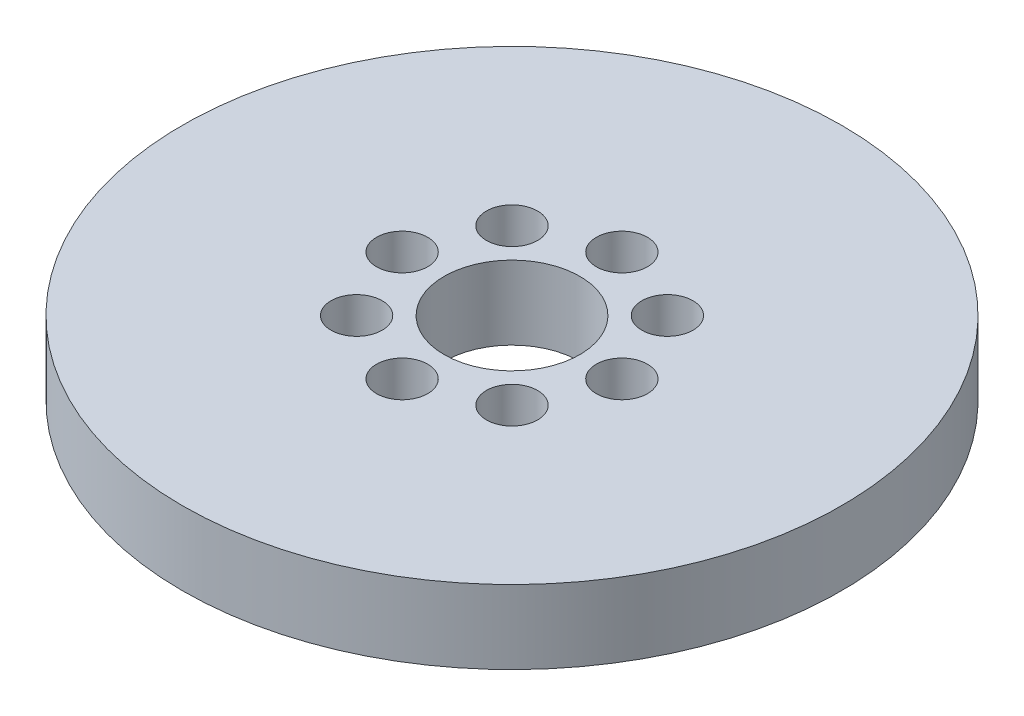
SolidWorks part; units mm, degrees
ref_plane "Front Plane" through (0, 0, 0) normal (0, 0, 1) x (1, 0, 0)
ref_plane "Top Plane" through (0, 0, 0) normal (0, 1, 0) x (1, 0, 0)
ref_plane "Right Plane" through (0, 0, 0) normal (1, 0, 0) x (0, 0, -1)
sketch "Sketch1" plane through (0, 0, 0) normal (0, 1, 0) x (1, 0, 0)
  circle A0 centre (0, 0) radius 85
  dimension "FLANGE_OD" = 170
extrude "Boss-Extrude1" add sketch "Sketch1" along normal blind 19
sketch "Sketch2" plane through (0, 0, 0) normal (0, 1, 0) x (1, 0, 0)
  circle A0 centre (0, 0) radius 17.5
  dimension "BORE_D" = 35
extrude "Cut-Extrude1" cut sketch "Sketch2" along normal through all
sketch "Sketch3" plane through (0, 19, 0) normal (0, 1, 0) x (1, 0, 0)
  circle A0 centre (0, 0) radius 28.3425 construction
  circle A1 centre (-28.3425, 0) radius 6.6004
  dimension "BOLT_D" = 13.2008
  dimension "BOLT_PCD" = 56.685
extrude "Cut-Extrude2" cut sketch "Sketch3" against normal blind 12.7052
pattern_circular "CirPattern1" count 8 over 360 about axis through (0, 0, 0) along (0, 1, 0) of "Cut-Extrude2"
